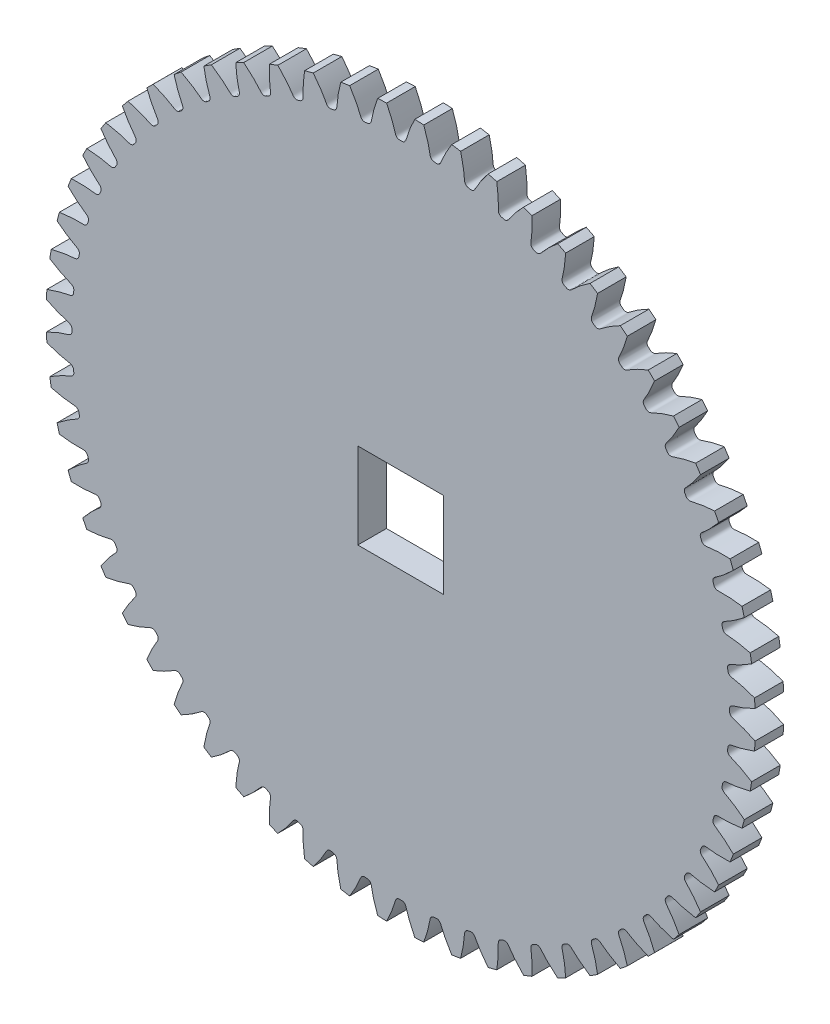
SolidWorks part; units mm, degrees
ref_plane "Alzado" through (0, 0, 0) normal (0, 0, 1) x (1, 0, 0)
ref_plane "Planta" through (0, 0, 0) normal (0, 1, 0) x (1, 0, 0)
ref_plane "Vista lateral" through (0, 0, 0) normal (1, 0, 0) x (0, 0, -1)
ref_axis "Eje1" through (0, 0, 0.275) along (0, 0, -1)
sketch "SketchRevolveEngranaje Fino(12.4)" plane through (0, 0, 0) normal (1, 0, 0) x (0, 0, -1)
  line L0 (0, 0) -> (1, 0) construction
  line L1 (-0.25, 0) -> (-0.25, 6.2)
  line L2 (-0.25, 6.2) -> (0.25, 6.2)
  line L3 (0.25, 6.2) -> (0.25, 0)
  line L4 (0.25, 0) -> (-0.25, 0)
revolve "Engranaje Fino(12.4)" add sketch "SketchRevolveEngranaje Fino(12.4)" angle 360 about L0
sketch "SketchToothEngranaje Fino(12.4)" plane through (0, 0, 0) normal (0, 0, 1) x (1, 0, 0)
  arc A0 (6.2049, 0.251) -> (6.2049, -0.251) centre (0, 0) cw
  spline S0 degree 3 poles (6.2049, -0.251) (6.18, -0.2382) (6.1468, -0.2219) (6.1055, -0.2028) (6.0819, -0.1922) (6.0587, -0.1821) (6.0362, -0.1725) (6.0141, -0.1635) (5.9927, -0.1549) (5.9718, -0.1469) (5.9514, -0.1394) (5.9317, -0.1323) (5.9125, -0.1256) (5.8939, -0.1194) (5.8759, -0.1137) (5.8586, -0.1083) (5.8401, -0.1029) (5.8262, -0.0987) (5.8163, -0.0962) (5.8123, -0.095) (5.8083, -0.0937) (5.8043, -0.0923) (5.8003, -0.0907) (5.7963, -0.089) (5.7922, -0.087) (5.7881, -0.0848) (5.7839, -0.0823) (5.7795, -0.0793) (5.775, -0.0758) (5.7703, -0.0715) (5.7656, -0.0663) (5.7608, -0.06) (5.7565, -0.0523) (5.7528, -0.0432) (5.7505, -0.0333) (5.7496, -0.0187) (5.7503, 0) (5.7496, 0.0187) (5.7505, 0.0333) (5.7528, 0.0432) (5.7565, 0.0523) (5.7608, 0.06) (5.7656, 0.0663) (5.7703, 0.0715) (5.775, 0.0758) (5.7795, 0.0793) (5.7839, 0.0823) (5.7881, 0.0848) (5.7922, 0.087) (5.7963, 0.089) (5.8003, 0.0907) (5.8043, 0.0923) (5.8083, 0.0937) (5.8123, 0.095) (5.8163, 0.0962) (5.8262, 0.0987) (5.8401, 0.1029) (5.8586, 0.1083) (5.8759, 0.1137) (5.8939, 0.1194) (5.9125, 0.1256) (5.9317, 0.1323) (5.9514, 0.1394) (5.9718, 0.1469) (5.9927, 0.1549) (6.0141, 0.1635) (6.0362, 0.1725) (6.0587, 0.1821) (6.0819, 0.1922) (6.1055, 0.2028) (6.1468, 0.2219) (6.18, 0.2382) (6.2049, 0.251) knots 0 0 0 0 0.076643 0.100908 0.124531 0.147511 0.16985 0.191547 0.212603 0.233016 0.252788 0.271918 0.290406 0.308252 0.325457 0.342019 0.35794 0.377966 0.381853 0.385707 0.389546 0.393393 0.397276 0.401231 0.405299 0.409534 0.414002 0.418784 0.423978 0.4297 0.436077 0.443235 0.451262 0.460162 0.469799 0.478976 0.5 0.521024 0.530201 0.539838 0.548738 0.556765 0.563923 0.5703 0.576022 0.581216 0.585998 0.590466 0.594701 0.598769 0.602724 0.606607 0.610454 0.614293 0.618147 0.622034 0.64206 0.657981 0.674543 0.691748 0.709594 0.728082 0.747212 0.766984 0.787397 0.808453 0.83015 0.852489 0.875469 0.899092 0.923357 1 1 1 1
extrude "ToothExtrudeCutEngranaje Fino(12.4)" cut sketch "SketchToothEngranaje Fino(12.4)" against normal blind 0.25 and the other way blind 0.25
pattern_circular "PatternEngranaje Fino(12.4)" count 60 every 6 about axis through (0, 0, 0.275) along (0, 0, -1) of "ToothExtrudeCutEngranaje Fino(12.4)"
sketch "AuxiliarySketchEngranaje Fino(12.4)" plane through (0, 0, 0) normal (0, 0, 1) x (1, 0, 0)
  circle A0 centre (0, 0) radius 6 construction
  circle A1 centre (0, 0) radius 5.6382 construction
  circle A2 centre (0, 0) radius 5.8183 construction
  circle A3 centre (0, 0) radius 6.2 construction
  circle A4 centre (0, 0) radius 5.75 construction
  dimension "PitchDiameter" = 12
  dimension "BaseDiameter" = 11.2763
  dimension "FormDiameter" = 11.6366
  dimension "MajorDiameter" = 12.4
  dimension "MinorDiameter" = 11.5
sketch "Croquis1" plane through (0, 0, 0.25) normal (0, 0, 1) x (1, 0, 0)
  line L1 (-0.75, 0.75) -> (0.75, 0.75)
  line L2 (-0.75, 0.75) -> (-0.75, -0.75)
  line L3 (-0.75, -0.75) -> (0.75, -0.75)
  line L4 (0.75, 0.75) -> (0.75, -0.75)
  point P4 (-0.75, 0)
  point P6 (0, 0.75)
  dimension "D1" = 1.5
  dimension "D2" = 1.5
extrude "Cortar-Extruir1" cut sketch "Croquis1" against normal blind 10
